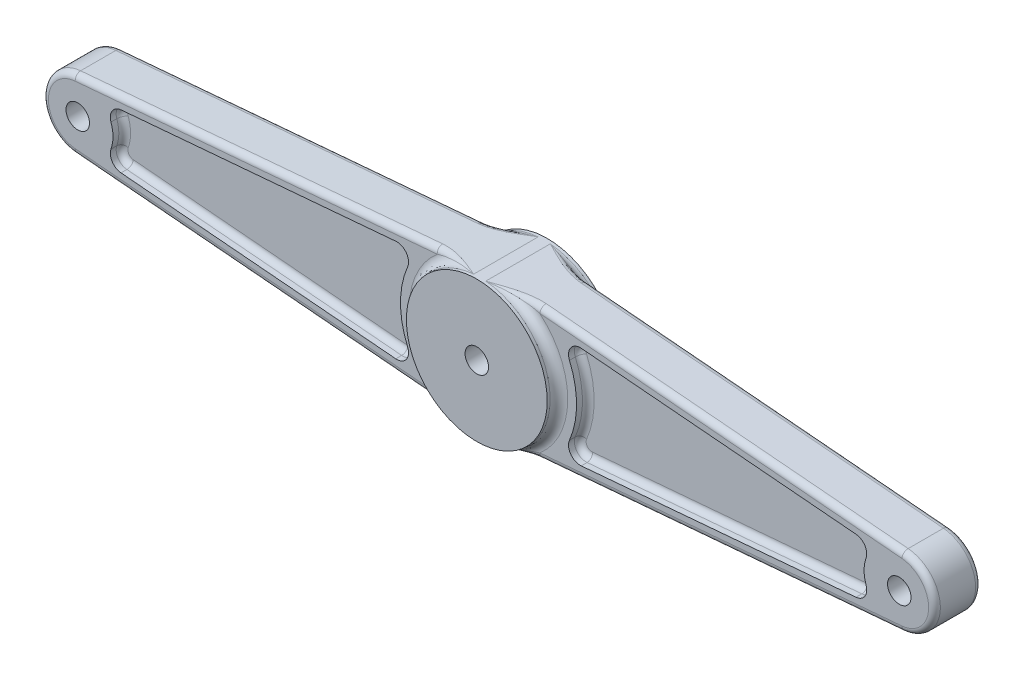
SolidWorks part; units mm, degrees
ref_plane "Front Plane" through (0, 0, 0) normal (0, 0, 1) x (1, 0, 0)
ref_plane "Top Plane" through (0, 0, 0) normal (0, 1, 0) x (1, 0, 0)
ref_plane "Right Plane" through (0, 0, 0) normal (1, 0, 0) x (0, 0, -1)
sketch "Sketch1" plane through (0, 0, 0) normal (0, 0, 1) x (1, 0, 0)
  circle A0 centre (0, 0) radius 12
  dimension "D1" = 24
extrude "Boss-Extrude1" add sketch "Sketch1" along normal mid plane 12
sketch "Sketch2" plane through (0, 0, 0) normal (0, 0, 1) x (1, 0, 0)
  line L0 (0, 0) -> (70, 0) construction
  line L1 (0, 12.0443) -> (70.5143, 5.9779)
  line L2 (1.0286, -11.9558) -> (70.5143, -5.9779)
  circle A0 centre (70, 0) radius 2
  circle A1 centre (70, 0) radius 6
  circle A2 centre (0, 0) radius 12 construction
  arc A3 (1.0286, -11.9558) -> (1.0286, 11.9558) centre (0, 0) ccw
  dimension "D2" = 12
  dimension "D3" = 4
  dimension "D1" = 70
extrude "Boss-Extrude2" add sketch "Sketch2" along normal mid plane 8 contours L0 A3 L2 A1 | A3 L0 A1 L1 | A1 A0 region at (35.0131, 4.7126, 0) region at (35.0131, -4.7126, 0) region at (66.058, 4.2957, 0)
mirror "Mirror1" about plane through (0, 0, 0) normal (1, 0, 0) of "Boss-Extrude2"
sketch "Sketch3" plane through (0, 0, 4) normal (0, 0, 1) x (1, 0, 0)
  line L0 (0, 0) -> (70, 0) construction
  line L1 (15.8019, 8.6775) -> (62.6254, 4.6492)
  line L2 (15.8019, -8.6775) -> (62.6254, -4.6492)
  line L3 (1.0286, 11.9558) -> (70.5143, 5.9779) construction
  arc A0 (13.7916, -5.8984) -> (13.7916, 5.8984) centre (0, 0) ccw
  arc A1 (64.3405, 1.9924) -> (64.3405, -1.9924) centre (70, 0) ccw
  circle A2 centre (0, 0) radius 12 construction
  arc A3 (62.6254, -4.6492) -> (64.3405, -1.9924) centre (62.454, -2.6566) ccw
  arc A4 (62.6254, 4.6492) -> (64.3405, 1.9924) centre (62.454, 2.6566) cw
  arc A5 (15.8019, -8.6775) -> (13.7916, -5.8984) centre (15.6305, -6.6848) cw
  arc A6 (15.8019, 8.6775) -> (13.7916, 5.8984) centre (15.6305, 6.6848) ccw
  point P15 (65.8872, -4.3686)
  point P18 (65.8872, 4.3686)
  point P21 (11.9963, -9.0049)
  point P24 (11.9963, 9.0049)
  dimension "D1" = 12
  dimension "D2" = 3
  dimension "D4" = 2
  dimension "D3" = 2
extrude "Cut-Extrude1" cut sketch "Sketch3" against normal blind 2
mirror "Mirror2" about plane through (0, 0, 0) normal (0, 0, 1) of "Cut-Extrude1"
mirror "Mirror3" about plane through (0, 0, 0) normal (1, 0, 0) of "Mirror2", "Cut-Extrude1"
fillet "Fillet1" radius 1 32 edges at (-14.01, -7.857, -2) (-15, 0, -2) (-14.01, 7.857, -2) (-39.2137, 6.6634, -2) (-64.1343, 3.7413, -2) (-64, 0, -2) (-64.1343, -3.7413, -2) (14.01, 7.857, -2) (39.2137, 6.6634, -2) (64.1343, 3.7413, -2) (64, 0, -2) (64.1343, -3.7413, -2) (39.2137, -6.6634, -2) (14.01, -7.857, -2) (14.01, -7.857, 2) (15, 0, 2) (14.01, 7.857, 2) (39.2137, 6.6634, 2) (64.1343, 3.7413, 2) (64, 0, 2) (64.1343, -3.7413, 2) (-14.01, -7.857, 2) (-15, 0, 2) (-14.01, 7.857, 2) (-39.2137, 6.6634, 2) (-64.1343, 3.7413, 2) (-64, 0, 2) (-64.1343, -3.7413, 2) (-39.2137, -6.6634, -2) (15, 0, -2) (39.2137, -6.6634, 2) (-39.2137, -6.6634, 2)
fillet "Fillet2" radius 1.5 4 edges at (-12, 0, -4) (12, 0, -4) (-12, 0, 4) (12, 0, 4)
fillet "Fillet3" radius 1 20 edges at (4.2015, -11.6829, -4.4638) (4.2015, 11.6829, -4.4638) (38.8524, 8.7018, -4) (76, 0, -4) (4.2015, -11.6829, 4.4638) (4.2015, 11.6829, 4.4638) (38.8524, 8.7018, 4) (76, 0, 4) (-4.2015, -11.6829, 4.4638) (-4.2015, 11.6829, 4.4638) (-38.8524, 8.7018, 4) (-76, 0, 4) (-4.2015, -11.6829, -4.4638) (-4.2015, 11.6829, -4.4638) (-38.8524, 8.7018, -4) (-76, 0, -4) (38.8524, -8.7018, -4) (38.8524, -8.7018, 4) (-38.8524, -8.7018, 4) (-38.8524, -8.7018, -4)
sketch "Sketch4" plane through (0, 0, -6) normal (0, 0, -1) x (-1, 0, 0)
  circle A0 centre (0, 0) radius 2
  dimension "D1" = 4
extrude "Cut-Extrude2" cut sketch "Sketch4" against normal through all
